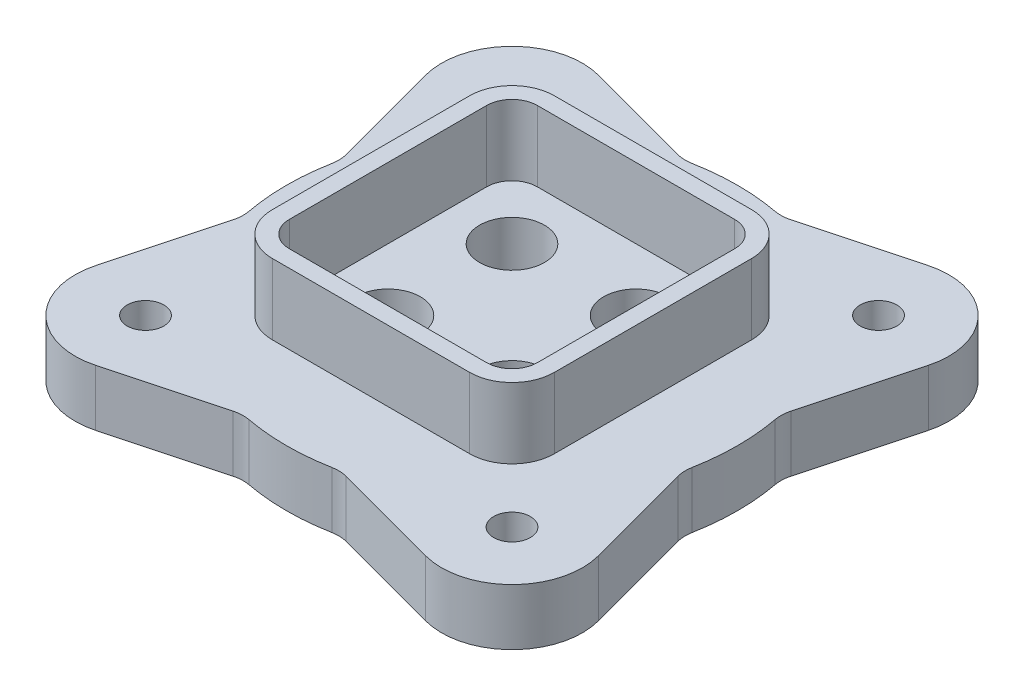
SolidWorks part; units mm, degrees
ref_plane "Front Plane" through (0, 0, 0) normal (0, 0, 1) x (1, 0, 0)
ref_plane "Top Plane" through (0, 0, 0) normal (0, 1, 0) x (1, 0, 0)
ref_plane "Right Plane" through (0, 0, 0) normal (1, 0, 0) x (0, 0, -1)
sketch "Sketch1" plane through (0, 0, 0) normal (0, 1, 0) x (1, 0, 0)
  line L0 (-89.1481, 58.5295) -> (-78.1042, 17.3129)
  line L5 (0, 0) -> (0, 23.6614) construction
  line L6 (0, 23.6614) -> (0, 0) construction
  line L7 (-58.5295, 89.1481) -> (-17.3129, 78.1042)
  line L8 (89.1481, 58.5295) -> (78.1042, 17.3129)
  line L9 (58.5295, 89.1481) -> (17.3129, 78.1042)
  line L10 (58.5295, -89.1481) -> (17.3129, -78.1042)
  line L11 (89.1481, -58.5295) -> (78.1042, -17.3129)
  line L12 (-89.1481, -58.5295) -> (-78.1042, -17.3129)
  line L13 (-58.5295, -89.1481) -> (-17.3129, -78.1042)
  line L14 (65, -65) -> (-65, 65) construction
  line L16 (0, 0) -> (28.6817, 0) construction
  circle A1 centre (-65, 65) radius 6.5
  arc A3 (-78.1042, 17.3129) -> (-78.1042, -17.3129) centre (0, 0) ccw
  arc A5 (89.1481, 58.5295) -> (58.5295, 89.1481) centre (65, 65) ccw
  circle A6 centre (65, 65) radius 6.5
  arc A8 (58.5295, -89.1481) -> (89.1481, -58.5295) centre (65, -65) ccw
  circle A9 centre (65, -65) radius 6.5
  arc A11 (-89.1481, -58.5295) -> (-58.5295, -89.1481) centre (-65, -65) ccw
  circle A12 centre (-65, -65) radius 6.5
  arc A14 (-58.5295, 89.1481) -> (-89.1481, 58.5295) centre (-65, 65) ccw
  arc A15 (17.3129, 78.1042) -> (-17.3129, 78.1042) centre (0, 0) ccw
  arc A17 (-17.3129, -78.1042) -> (17.3129, -78.1042) centre (0, 0) ccw
  arc A18 (78.1042, -17.3129) -> (78.1042, 17.3129) centre (0, 0) ccw
  point P0 (0, 0)
  point P47 (0, 0)
  dimension "D4" = 13
  dimension "D5" = 60
  dimension "D6" = 160
  dimension "D1" = 25
  dimension "D3" = 65
  dimension "D9" = 4
extrude "Boss-Extrude1" add sketch "Sketch1" along normal blind 20
sketch "Sketch2" plane through (0, 20, 0) normal (0, 1, 0) x (1, 0, 0)
  line L1 (-35, -50) -> (35, -50)
  line L2 (-50, -35) -> (-50, 35)
  line L3 (-35, 50) -> (35, 50)
  line L4 (50, -35) -> (50, 35)
  line L5 (-50, -50) -> (50, 50) construction
  line L6 (-50, 50) -> (50, -50) construction
  line L10 (-44, -35) -> (-44, 35)
  line L11 (-35, 44) -> (35, 44)
  line L12 (44, -35) -> (44, 35)
  line L13 (-35, -44) -> (35, -44)
  line L15 (0, 0) -> (-113.5979, 0) construction
  line L17 (0, 0) -> (0, 10.8418) construction
  circle A0 centre (-22, 22) radius 11.5
  circle A1 centre (22, 22) radius 11.5
  circle A2 centre (22, -22) radius 11.5
  circle A3 centre (-22, -22) radius 11.5
  arc A4 (35, -50) -> (50, -35) centre (35, -35) ccw
  arc A5 (35, 50) -> (50, 35) centre (35, 35) cw
  arc A6 (-50, 35) -> (-35, 50) centre (-35, 35) cw
  arc A7 (-35, -50) -> (-50, -35) centre (-35, -35) cw
  arc A8 (-44, 35) -> (-35, 44) centre (-35, 35) cw
  arc A9 (35, 44) -> (44, 35) centre (35, 35) cw
  arc A10 (35, -44) -> (44, -35) centre (35, -35) ccw
  arc A11 (-35, -44) -> (-44, -35) centre (-35, -35) cw
  point P0 (0, 0)
  point P21 (0, 0)
  dimension "D3" = 22
  dimension "D4" = 23
  dimension "D2" = 15
  dimension "D1" = 100
  dimension "D6" = 6
  dimension "D5" = 4
extrude "Cut-Extrude1" cut sketch "Sketch2" against normal through all contours A3 | A0 | A1 | A2 region at (-22, 20, -22) region at (22, 20, -22) region at (22, 20, 22) region at (-22, 20, 22)
extrude "Boss-Extrude2" add sketch "Sketch2<3>" along normal blind 25 contours L1 L4 L3 L2 A4 region at (-44.6066, 20, 44.6066)
sketch "Sketch2<3>" plane through (0, 20, 0) normal (0, 1, 0) x (1, 0, 0) same geometry as "Sketch2"
sketch "Sketch3" plane through (0, 0, 0) normal (0, -1, 0) x (1, 0, 0)
  circle A0 centre (0, 0) radius 72.5
  circle A1 centre (0, 0) radius 52.5
  dimension "D1" = 105
  dimension "D2" = 145
extrude "Cut-Extrude2" cut sketch "Sketch3" against normal blind 3
fillet "Fillet2" radius 12 8 edges at (-17.3129, 10, -78.1042) (17.3129, 10, -78.1042) (17.3129, 10, 78.1042) (-17.3129, 10, 78.1042) (-78.1042, 10, 17.3129) (-78.1042, 10, -17.3129) (78.1042, 10, -17.3129) (78.1042, 10, 17.3129)
